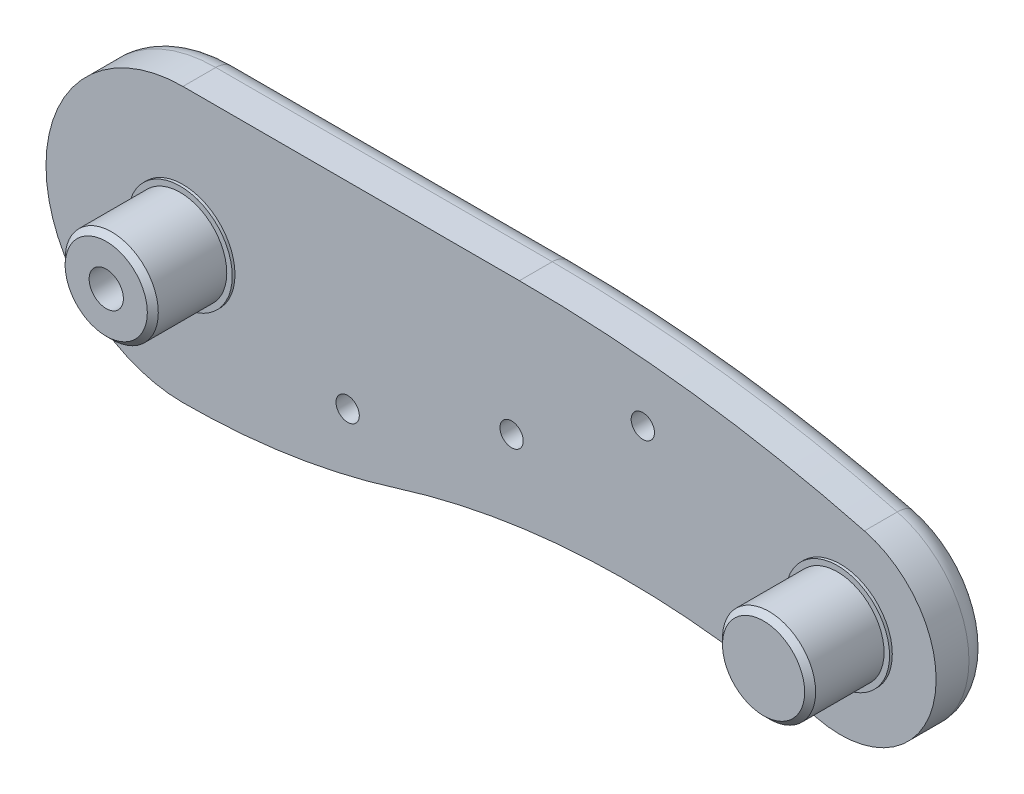
SolidWorks part; units mm, degrees
ref_plane "Front Plane" through (0, 0, 0) normal (0, 0, 1) x (1, 0, 0)
ref_plane "Top Plane" through (0, 0, 0) normal (0, 1, 0) x (1, 0, 0)
ref_plane "Right Plane" through (0, 0, 0) normal (1, 0, 0) x (0, 0, -1)
sketch "Sketch1" plane through (0, 0, 0) normal (0, 0, 1) x (1, 0, 0)
  line L0 (0, 25) -> (61.4231, 25)
  line L1 (0, 0) -> (120, 0) construction
  line L2 (0, 0) -> (0, -25) construction
  circle A0 centre (0, 0) radius 25
  circle A1 centre (120, 0) radius 17.5
  arc A2 (61.4231, 25) -> (124.409, 16.9355) centre (61.4231, -225) cw
  arc A3 (115.6605, -16.9534) -> (38.9734, -19.0205) centre (80.9448, -152.5809) ccw
  arc A4 (0, -25) -> (38.9734, -19.0205) centre (0, 105) ccw
  dimension "D1" = 50
  dimension "D3" = 35
  dimension "D4" = 130
  dimension "D5" = 140
  dimension "D6" = 250
  dimension "D2" = 120
extrude "Boss-Extrude1" add sketch "Sketch1" along normal blind 6 contours A0 A4 A3 A1 A2 L0 | A0 | A1 region at (60.7118, 4.4003, 0) region at (0, 0, 0) region at (120, 0, 0)
sketch "Sketch3" plane through (0, 0, 0) normal (0, 0, -1) x (-1, 0, 0)
  circle A0 centre (0, 0) radius 10
  circle A1 centre (0, 0) radius 25
  arc A2 (0, -25) -> (0, 25) centre (0, 0) ccw construction
  line M1 (0, 25) -> (-61.4231, 25)
  arc M2 (-61.4231, 25) -> (-124.409, 16.9355) centre (-61.4231, -225) ccw
  arc M3 (-124.409, 16.9355) -> (-115.6605, -16.9534) centre (-120, 0) ccw
  arc M4 (-115.6605, -16.9534) -> (-38.9734, -19.0205) centre (-80.9448, -152.5809) cw
  arc M5 (-38.9734, -19.0205) -> (0, -25) centre (0, 105) ccw
  arc M6 (0, -25) -> (0, 25) centre (0, 0) ccw
  dimension "D1" = 20
extrude "Boss-Extrude3" add sketch "Sketch3" along normal blind 4 contours A1 M1 M2 M3 M4 M5 | A1 A0 M6 region at (-17.1777, -17.1777, 0) region at (73.5538, 3.4472, 0)
sketch "Sketch4" plane through (0, 0, 6) normal (0, 0, 1) x (1, 0, 0)
  circle A0 centre (0, 0) radius 8.5
  circle A1 centre (120, 0) radius 8.5
  dimension "D1" = 17
  dimension "D2" = 17
extrude "Boss-Extrude4" add sketch "Sketch4" along normal blind 14
sketch "Sketch5" plane through (0, 0, -4) normal (0, 0, -1) x (-1, 0, 0)
  line L0 (0, 0) -> (-60, 0) construction
  line L1 (0, 0) -> (-83.9535, 13.2969) construction
  line L2 (0, 0) -> (-30.0702, -10.9446) construction
  circle A0 centre (-83.9535, 13.2969) radius 2.125
  circle A1 centre (-60, 0) radius 2.125
  circle A2 centre (-30.0702, -10.9446) radius 2.125
  dimension "D6" = 4.25
  dimension "D1" = 20
  dimension "D2" = 9
  dimension "D3" = 85
  dimension "D4" = 60
  dimension "D5" = 32
extrude "Cut-Extrude1" cut sketch "Sketch5" against normal through all
sketch "Sketch6" plane through (0, 0, -4) normal (0, 0, -1) x (-1, 0, 0)
  circle A0 centre (-83.9535, 13.2969) radius 3.75
  circle A1 centre (-60, 0) radius 3.75
  circle A2 centre (-30.0702, -10.9446) radius 3.75
  dimension "D1" = 7.5
extrude "Cut-Extrude2" cut sketch "Sketch6" against normal blind 4.25
fillet "Fillet1" radius 4 6 edges at (-25, 0, -4) (19.7147, -23.4964, -4) (77.1726, -12.6318, -4) (136.9445, -4.3742, -4) (93.1732, 22.9757, -4) (30.7116, 25, -4)
sketch "Sketch7" plane through (0, 0, 6) normal (0, 0, 1) x (1, 0, 0)
  circle A0 centre (0, 0) radius 9.5
  circle A1 centre (0, 0) radius 8.5 construction
  circle A2 centre (120, 0) radius 9.5
  circle A3 centre (0, 0) radius 8.5
  circle A4 centre (0, 0) radius 8.5
  circle A5 centre (120, 0) radius 8.5 construction
  circle A6 centre (120, 0) radius 8.5
  dimension "D1" = 1
  dimension "D3" = 1
  dimension "D2" = 0
extrude "Boss-Extrude5" add sketch "Sketch7" along normal blind 0.5
chamfer "Chamfer2" distance 1 angle 45 2 edges at (8.5, 0, 20) (128.5, 0, 20)
sketch "Sketch8" plane through (0, 0, 0) normal (0, 0, -1) x (-1, 0, 0)
  circle A0 centre (0, 0) radius 1.625
  dimension "D1" = 3.25
extrude "Cut-Extrude3" cut sketch "Sketch8" against normal through all
sketch "Sketch9" plane through (0, 0, 20) normal (0, 0, 1) x (1, 0, 0)
  circle A0 centre (0, 0) radius 3.125
  dimension "D1" = 6.25
extrude "Cut-Extrude4" cut sketch "Sketch9" against normal blind 17
sketch "Sketch10" plane through (0, 0, 0) normal (0, 0, -1) x (-1, 0, 0)
  line L0 (0, 0) -> (0, 7.42) construction
  circle A0 centre (0, 0) radius 7.42 construction
  circle A1 centre (0, 7.42) radius 1
  circle A2 centre (7.42, 0) radius 1
  circle A3 centre (0, -7.42) radius 1
  circle A4 centre (-7.42, 0) radius 1
  point P14 (0, 0)
  dimension "D1" = 14.84
  dimension "D2" = 2
  dimension "D3" = 4
extrude "Cut-Extrude5" cut sketch "Sketch10" against normal blind 4
sketch "Sketch11" plane through (0, 0, -4) normal (0, 0, -1) x (-1, 0, 0)
  circle A0 centre (0, 0) radius 14
  circle A1 centre (0, 0) radius 10 construction
  circle A2 centre (0, 0) radius 10
  dimension "D1" = 4
extrude "Boss-Extrude6" add sketch "Sketch11" along normal blind 2
chamfer "Chamfer3" distance 4 angle 45 1 edges at (-14, 0, -4)
